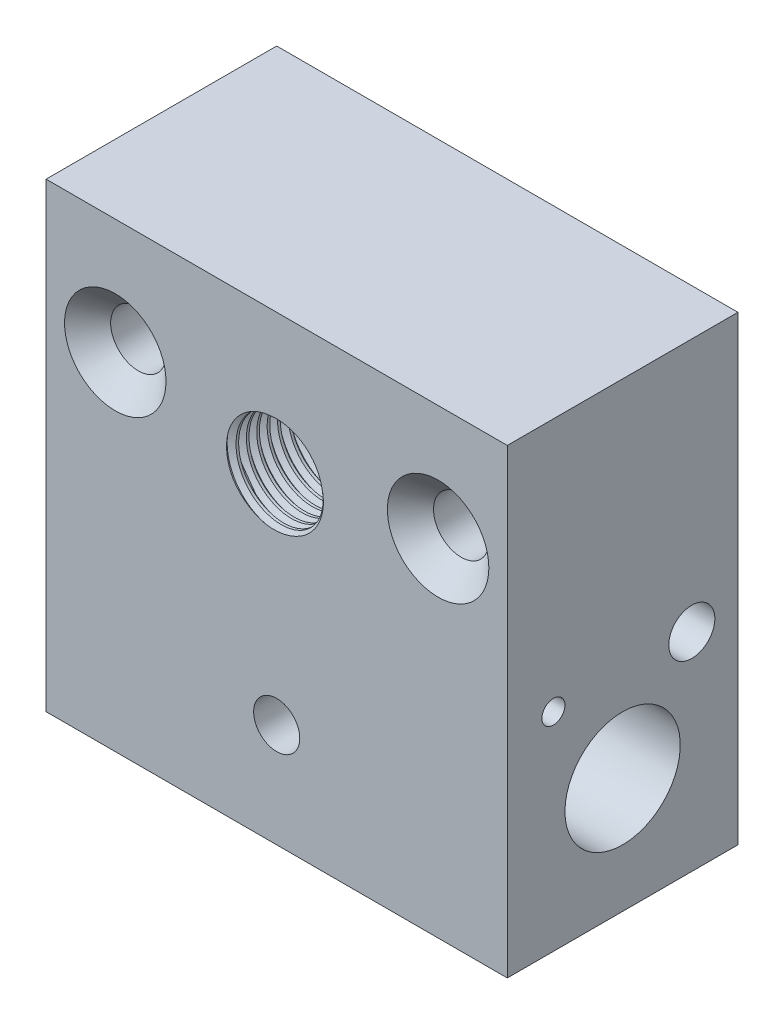
SolidWorks part; units mm, degrees
ref_plane "Front Plane" through (0, 0, 0) normal (0, 0, 1) x (1, 0, 0)
ref_plane "Top Plane" through (0, 0, 0) normal (0, 1, 0) x (1, 0, 0)
ref_plane "Right Plane" through (0, 0, 0) normal (1, 0, 0) x (0, 0, -1)
sketch "Sketch1" plane through (0, 0, 0) normal (0, 1, 0) x (1, 0, 0)
  line L1 (-10, -5) -> (10, -5)
  line L2 (-10, -5) -> (-10, 5)
  line L3 (-10, 5) -> (10, 5)
  line L4 (10, -5) -> (10, 5)
  line L5 (-10, -5) -> (10, 5) construction
  line L6 (-10, 5) -> (10, -5) construction
  point P0 (0, 0)
  dimension "D1" = 20
  dimension "D2" = 10
extrude "Boss-Extrude1" add sketch "Sketch1" along normal blind 20
hole_wizard "CSK for M2 Flat Head Machine Screw1" positions "Sketch2" profile "Sketch3" countersink size "M2" standard "ANSI Metric" end condition through all
sketch "Sketch2" plane through (0, 0, 5) normal (0, 0, 1) x (1, 0, 0)
  line L0 (7, 20) -> (7, 15) construction
  line L1 (-10, 20) -> (10, 20) construction
  line L2 (7, 15) -> (10, 15) construction
  line L3 (10, 20) -> (10, 0) construction
  line L5 (-7, 20) -> (-7, 15) construction
  line L6 (-7, 15) -> (-10, 15) construction
  line L7 (-10, 20) -> (-10, 0) construction
  point P0 (7, 15)
  point P2 (-7, 15)
  dimension "D1" = 5
  dimension "D2" = 3
sketch "Sketch3" plane through (7, 15, 5) normal (1, 0, 0) x (0, -1, 0)
  line L0 (0, 0) -> (0, 10)
  line L1 (0, 10) -> (1.2, 10)
  line L2 (1.2, 10) -> (1.2, 1)
  line L3 (1.2, 1) -> (2.2, 0)
  line L5 (2.2, 0) -> (0, 0)
  line L6 (-1.2, 1) -> (-2.2, 0) construction
  line L11 (0, -6.35) -> (0, 107.95) construction
  dimension "Thru Hole Dia." = 2.4
  dimension "Thru Hole Depth" = 10
  dimension "Near C'Sink Dia." = 4.4
  dimension "Near C'Sink Angle" = 90
sketch "Sketch6" plane through (0, 0, 5) normal (0, 0, 1) x (1, 0, 0)
  line L0 (0, 14) -> (0, 20) construction
  line L1 (-10, 20) -> (10, 20) construction
  line L2 (0, 4.5) -> (0, 0) construction
  circle A0 centre (0, 14) radius 2
  circle A1 centre (0, 4.5) radius 1
  dimension "D1" = 4
  dimension "D2" = 2
  dimension "D3" = 4.5
  dimension "D4" = 6
extrude "Cut-Extrude1" cut sketch "Sketch6" against normal through all contours A0 | A0 region at (0, 14, 5)
extrude "Cut-Extrude3" cut sketch "Sketch6<3>" against normal blind 5 contours A1 region at (0, 4.5, 5)
sketch "Sketch6<3>" plane through (0, 0, 5) normal (0, 0, 1) x (1, 0, 0) same geometry as "Sketch6"
thread "Thread1" pitch 0.45 method cut profile "Thread Profile1" start angle 0, offset 1, length 0, pitch 0.45, diameter 4
ref_plane "Plane1" through (-2, 14, 6) normal (0, -1, 0) x (-1, 0, 0)
sketch "Thread Profile1" plane through (-2, 14, 6) normal (0, -1, 0) x (-1, 0, 0)
  line L0 (0, 0) -> (0, 0.45) construction
  line L1 (0, 0) -> (0.2436, 0.1406)
  line L2 (0.2436, 0.1406) -> (0.2436, 0.1969)
  line L3 (0.2436, 0.1969) -> (0, 0.3375)
  line L4 (0.2436, 0.1687) -> (0, 0.1687) construction
  line L11 (0, 0) -> (0, 0.3375)
  point P2 (0, 0)
  dimension "Pitch" = 0.45
  dimension "Profile_Angle" = 60
  dimension "Profile_Land" = 0.0562
  dimension "Profile_Height" = 0.2436
sketch "Sketch13" plane through (-10, 0, 0) normal (-1, 0, 0) x (0, 0, 1)
  line L0 (0, 5) -> (0, 0) construction
  line L1 (-3, 9) -> (-5, 9) construction
  line L3 (-5, 20) -> (-5, 0) construction
  line L4 (3, 9) -> (5, 9) construction
  line L5 (5, 20) -> (5, 0) construction
  line L6 (-3, 9) -> (-3, 20) construction
  line L7 (-5, 20) -> (5, 20) construction
  line L8 (3, 9) -> (3, 20) construction
  circle A0 centre (0, 5) radius 2.5
  circle A1 centre (-3, 9) radius 1
  circle A2 centre (3, 9) radius 0.5
  dimension "D1" = 1
  dimension "D2" = 2
  dimension "D3" = 5
  dimension "D4" = 5
  dimension "D5" = 11
  dimension "D6" = 2
extrude "Cut-Extrude2" cut sketch "Sketch13" against normal through all
